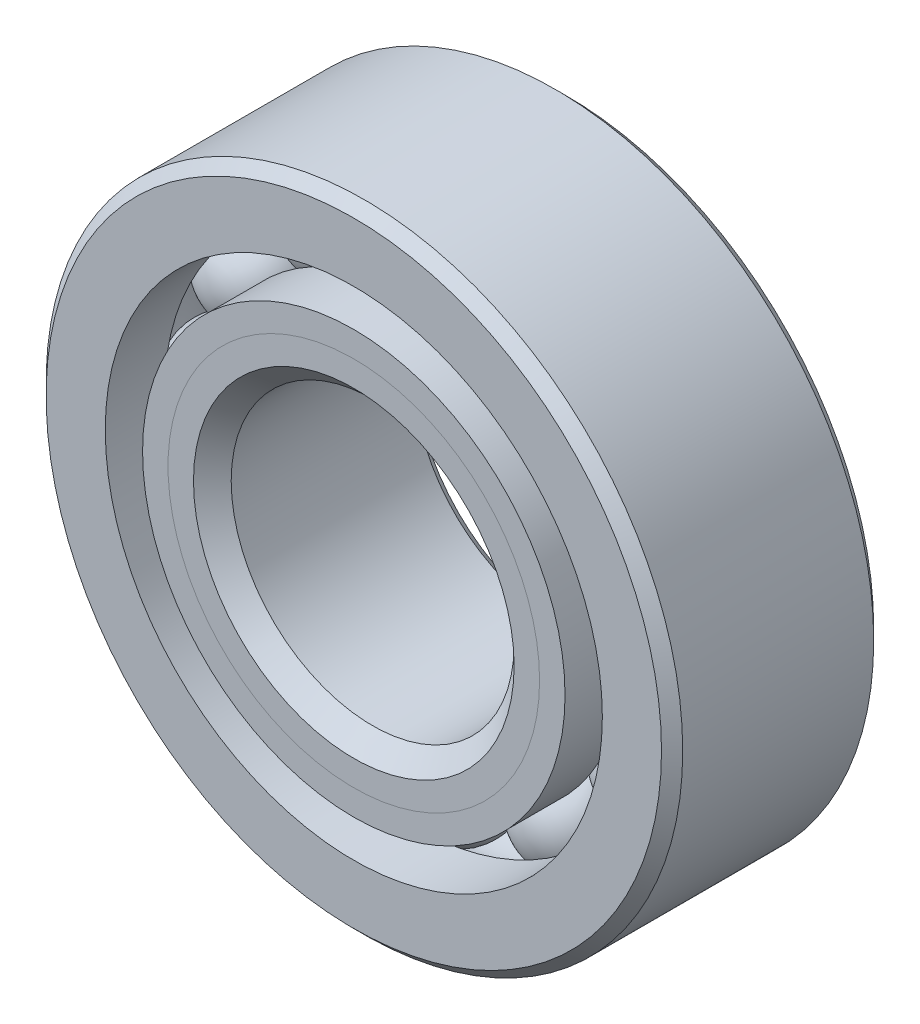
SolidWorks part; units mm, degrees
material "Plain Carbon Steel"
ref_plane "Front Plane" through (0, 0, 0) normal (0, 0, 1) x (1, 0, 0)
ref_plane "Top Plane" through (0, 0, 0) normal (0, 1, 0) x (1, 0, 0)
ref_plane "Right Plane" through (0, 0, 0) normal (1, 0, 0) x (0, 0, -1)
sketch "Sketch1" plane through (0, 0, 0) normal (1, 0, 0) x (0, 0, -1)
  line L0 (-4.7625, 0) -> (4.7625, 0) construction
  line L1 (0, 14.2875) -> (0, -14.2875) construction
  line L2 (4.2863, 14.2875) -> (-4.2863, 14.2875)
  line L3 (-4.2863, 14.2875) -> (-4.7625, 13.8112)
  line L4 (-4.7625, 13.8112) -> (-4.7625, 11.1561)
  line L5 (-4.7625, 11.1561) -> (-2.1167, 11.1561)
  line L6 (4.7625, 11.1561) -> (2.1167, 11.1561)
  line L7 (4.7625, 13.8113) -> (4.7625, 11.1561)
  line L8 (4.2863, 14.2875) -> (4.7625, 13.8113)
  line L9 (0, 14.2875) -> (0, 10.3187) construction
  line L10 (0, 10.3187) -> (0, 6.35) construction
  arc A0 (-2.1167, 11.1561) -> (2.1167, 11.1561) centre (0, 10.3187) cw
  point P14 (0, 6.35)
  dimension "Width" = 9.525
  dimension "OD" = 28.575
  dimension "D1" = 45
  dimension "D2" = 0.4763
  dimension "D3" = 4.2333
  dimension "D4" = 0.8374
revolve "Revolve1" add sketch "Sketch1" angle 360 about L0
sketch "Sketch2" plane through (0, 0, 0) normal (1, 0, 0) x (0, 0, -1)
  line L0 (-4.7625, 9.4814) -> (-2.1167, 9.4814)
  line L1 (-4.7625, 13.8112) -> (-4.7625, -13.8112) construction
  line L2 (-4.7625, 9.4814) -> (-4.7625, 8.3388)
  line L3 (-4.7625, 8.3388) -> (-3.6199, 7.1962)
  line L4 (-3.6199, 7.1962) -> (0, 7.1962)
  line L5 (0, 14.2875) -> (0, -14.2875) construction
  line L6 (0, 7.1962) -> (0, 8.0425)
  line L7 (0, 8.0425) -> (0, 6.35) construction
  line L8 (-4.7625, 9.4814) -> (-4.7625, 7.1962) construction
  line L9 (-4.7625, 7.1962) -> (-3.6199, 7.1962) construction
  arc A0 (-2.1167, 9.4814) -> (0, 8.0425) centre (0, 10.3187) ccw
  arc A1 (2.1167, 11.1561) -> (-2.1167, 11.1561) centre (0, 10.3187) ccw construction
  circle A2 centre (0, 10.3187) radius 2.2763 construction
  dimension "D1" = 45
revolve "Revolve2" add sketch "Sketch2" angle 360 about L0
sketch "Sketch3" plane through (0, 0, 0) normal (1, 0, 0) x (0, 0, -1)
  line L0 (-4.7625, 8.3388) -> (-3.6199, 7.1962)
  line L1 (-3.6199, 7.1962) -> (0, 7.1962)
  line L2 (0, 7.1962) -> (0, 8.0425)
  line L3 (-4.7625, 8.3388) -> (-4.7625, 7.1962)
  line L4 (-4.7625, 9.4814) -> (-4.7625, 7.1962) construction
  line L5 (-4.7625, 7.1962) -> (-3.9163, 6.35)
  line L6 (-3.9163, 6.35) -> (4.2863, 6.35)
  line L7 (4.2863, 14.2875) -> (4.2863, -14.2875) construction
  line L8 (4.2863, 6.35) -> (4.7625, 6.8262)
  line L9 (4.7625, -13.8113) -> (4.7625, 13.8113) construction
  line L10 (4.7625, 6.8262) -> (4.7625, 9.4814)
  line L11 (4.7625, 9.4814) -> (2.1167, 9.4814)
  line L13 (4.2863, 14.2875) -> (4.7625, 13.8113) construction
  circle A0 centre (0, 10.3187) radius 2.2763 construction
  arc A1 (2.1167, 9.4814) -> (0, 8.0425) centre (0, 10.3187) cw
revolve "Revolve3" add sketch "Sketch3" angle 360 about L0
sketch "Sketch4" plane through (0, 0, 0) normal (1, 0, 0) x (0, 0, -1)
  line L0 (-2.2763, 10.3187) -> (2.2763, 10.3187)
  circle A1 centre (0, 10.3187) radius 2.2763 construction
  arc A2 (-2.2763, 10.3187) -> (2.2763, 10.3187) centre (0, 10.3187) cw
  arc A3 (2.1167, 11.1561) -> (-2.1167, 11.1561) centre (0, 10.3187) ccw construction
revolve "Revolve4" add sketch "Sketch4" angle 360 about L0
ref_axis "Axis1" through (0, 0, -4.7625) along (0, 0, 1)
pattern_circular "CirPattern1" count 12 every 30 about axis through (0, 0, -4.7625) along (0, 0, 1) of bodies 104
equation "\"D2@Sketch1\" = \"Width@Sketch1\"*.05"
equation "\"D3@Sketch1\" = \"Width@Sketch1\"/2.25"
equation "\"D4@Sketch1\" = (((\"OD@Sketch1\"-\"Width@Sketch1\")/2)/3.25)/3.5"
equation "\"D2@CirPattern1\" = 360/\"Balls@CirPattern1\""
